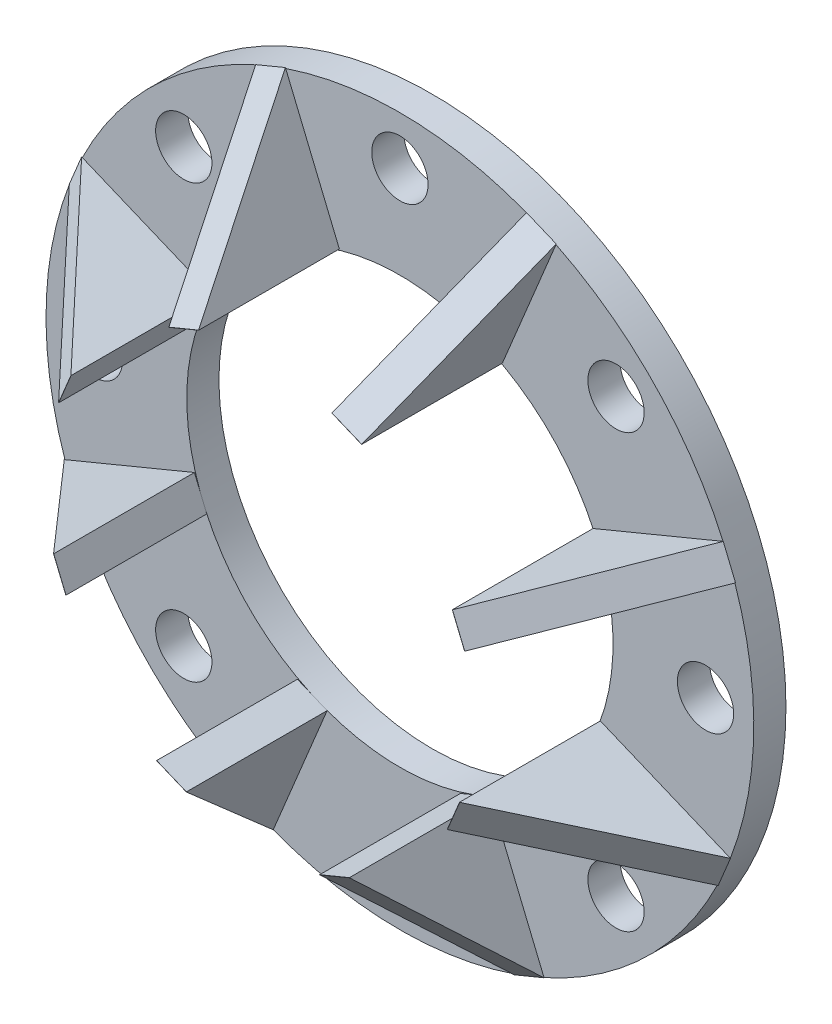
SolidWorks part; units mm, degrees
ref_plane "Front Plane" through (0, 0, 0) normal (0, 0, 1) x (1, 0, 0)
ref_plane "Top Plane" through (0, 0, 0) normal (0, 1, 0) x (1, 0, 0)
ref_plane "Right Plane" through (0, 0, 0) normal (1, 0, 0) x (0, 0, -1)
sketch "Sketch1" plane through (0, 0, 0) normal (0, 0, 1) x (1, 0, 0)
  circle A0 centre (0, 0) radius 84.1375
  circle A1 centre (0, 0) radius 139.7
  dimension "D1" = 168.275
  dimension "D2" = 279.4
extrude "Extrude1" add sketch "Sketch1" along normal blind 12.7
hole_wizard " (0.625) Diameter Hole1" positions "3DSketch1" profile "Sketch2" hole size "7/8" standard "Ansi Inch"
sketch3d "3DSketch1"
  line L10 (0, 139.7, 12.7) -> (0, 0, 12.7) construction
  circle A2 centre (0, 0, 12.7) radius 139.7 construction
  circle A3 centre (0, 0, 12.7) radius 139.7 construction
  point P5 (0, 120.65, 12.7)
  point P24 (0, 0, 152.4)
  point P26 (0, 0, 152.4)
  dimension "D1" = 120.65
sketch "Sketch2" plane through (0, 120.65, 12.7) normal (1, 0, 0) x (0, -1, 0)
  line L0 (0, 0) -> (0, 32.0771)
  line L1 (0, 32.0771) -> (11.1125, 25.4)
  line L2 (11.1125, 25.4) -> (11.1125, 0)
  line L5 (11.1125, 0) -> (0, 0)
  line L10 (0, 32.0771) -> (-11.1125, 25.4) construction
  line L11 (0, -6.35) -> (0, 107.95) construction
  dimension "Hole Dia." = 22.225
  dimension "Hole Depth" = 25.4
  dimension "Drill Angle" = 118
pattern_circular "CirPattern1" [suppressed] count 4 over 360 of bodies 102
pattern_circular "CirPattern2" count 8 over 360 about axis through (0, 0, 12.7) along (0, 0, -1) of " (0.625) Diameter Hole1"
sketch "Sketch4" plane through (0, 0, 12.7) normal (0, 0, 1) x (1, 0, 0)
  line L0 (0, 0) -> (0, 139.7) construction
  line L1 (0, 0) -> (-139.7, 0) construction
  line L2 (-99.3557, 98.2066) -> (-60.066, 58.9168) construction
  line L3 (-99.9167, 89.7873) -> (-68.4853, 58.3559)
  line L4 (-99.9167, 89.7873) -> (-90.9364, 98.7675)
  line L5 (-68.4853, 58.3559) -> (-59.5051, 67.3362)
  line L6 (-90.9364, 98.7675) -> (-59.5051, 67.3362)
  line L7 (-99.9167, 89.7873) -> (-59.5051, 67.3362) construction
  line L8 (-68.4853, 58.3559) -> (-90.9364, 98.7675) construction
  circle A0 centre (0, 0) radius 139.7 construction
  circle A1 centre (0, 0) radius 84.1375 construction
  point P12 (-79.7109, 78.5617)
  dimension "D1" = 45
  dimension "D2" = 12.7
extrude "Extrude2" [suppressed] add sketch "Sketch4" along normal blind 55.5625
sketch "Sketch5" [suppressed] plane through (-4.7316, -4.7316, 0) normal (-0.7071, -0.7071, 0) x (0, 0, 1)
  line L0 (57.15, 44.4487) -> (57.15, 88.8993)
  line L1 (57.15, 88.8993) -> (12.7, 88.8993)
  line L2 (12.7, 88.8993) -> (57.15, 44.4487)
extrude "Extrude3" [suppressed] cut sketch "Sketch5" against normal through all
pattern_circular "CirPattern3" [suppressed] count 4 over 360 of bodies 106
sketch "Sketch6" plane through (0, 0, 12.7) normal (0, 0, 1) x (1, 0, 0)
  line L0 (0, 0) -> (0, 139.7) construction
  line L1 (-56.9193, 127.6335) -> (-35.6358, 76.2506)
  line L2 (-51.0433, 130.041) -> (-29.7785, 78.7031) construction
  line L3 (-56.9193, 127.6335) -> (-45.186, 132.4935)
  line L4 (-35.6358, 76.2506) -> (-23.9025, 81.1107)
  line L5 (-45.186, 132.4935) -> (-23.9025, 81.1107)
  line L6 (-56.9193, 127.6335) -> (-23.9025, 81.1107) construction
  line L7 (-35.6358, 76.2506) -> (-45.186, 132.4935) construction
  circle A0 centre (0, 0) radius 139.7 construction
  point P9 (-40.4109, 104.3721)
  dimension "D1" = 22.5
  dimension "D2" = 12.7
extrude "Extrude4" add sketch "Sketch6" along normal blind 55.5625
chamfer "Chamfer1" distance 55.5625 distance2 55.5625 1 edges at (-51.0526, 130.0635, 68.2625)
pattern_circular "CirPattern4" count 8 over 360 about axis through (0, 0, 12.7) along (0, 0, -1) of "Extrude4", "Chamfer1"
equation "\"D1@Extrude2\" = (\"D2@Sketch1\" - \"D1@Sketch1\")/2"
equation "\"D1@Extrude4\" = (\"D2@Sketch1\" - \"D1@Sketch1\") / 2"
equation "\"D3@Chamfer1\" = \"D1@Extrude4\""
equation "\"D1@Chamfer1\" = \"D3@Chamfer1\""
